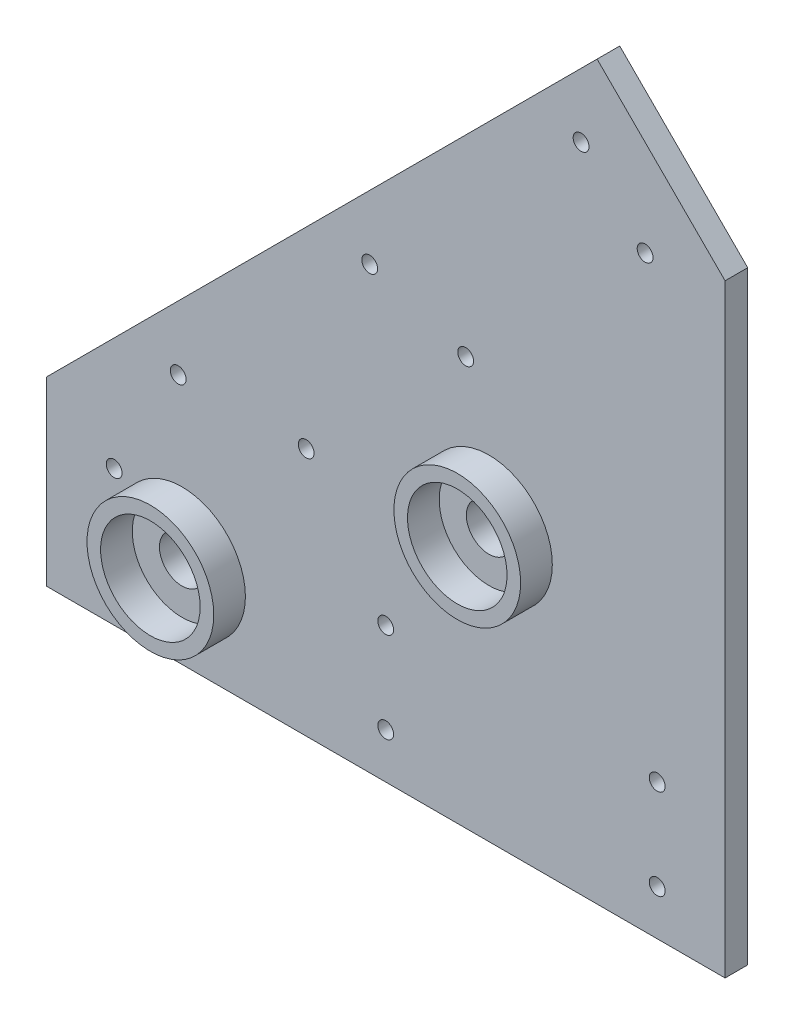
SolidWorks part; units mm, degrees
ref_plane "Front Plane" through (0, 0, 0) normal (0, 0, 1) x (1, 0, 0)
ref_plane "Top Plane" through (0, 0, 0) normal (0, 1, 0) x (1, 0, 0)
ref_plane "Right Plane" through (0, 0, 0) normal (1, 0, 0) x (0, 0, -1)
sketch "Sketch1" plane through (0, 0, 0) normal (0, 0, 1) x (1, 0, 0)
  line L0 (-75, 20) -> (46.7157, 141.7157)
  line L1 (-18.4315, 20) -> (75, 20) construction
  line L2 (-75, 20) -> (-75, -20)
  line L3 (-75, -20) -> (75, -20)
  line L4 (75, 20) -> (75, -20)
  line L5 (-75, 20) -> (75, -20) construction
  line L6 (-75, -20) -> (75, 20) construction
  line L7 (-75, -20) -> (75, -20)
  line L11 (46.7157, 141.7157) -> (75, 113.4315)
  line L12 (75, 113.4315) -> (-18.4315, 20) construction
  line L13 (-75, 0) -> (75, 0) construction
  line L14 (-75, 10) -> (75, 10) construction
  line L15 (-75, -10) -> (75, -10) construction
  line L16 (60.8579, 127.5736) -> (-46.7157, 20) construction
  line L17 (-75, 20) -> (-18.4315, 20) construction
  line L18 (53.7868, 134.6447) -> (-60.8579, 20) construction
  line L19 (67.9289, 120.5025) -> (-32.5736, 20) construction
  line L20 (75, 113.4315) -> (75, 20)
  line L21 (43.1802, 124.0381) -> (57.3223, 109.8959) construction
  line L22 (60, -10) -> (60, 10) construction
  line L23 (-60, -10) -> (-60, 10) construction
  circle A0 centre (-45, 0) radius 5
  circle A1 centre (22.8199, 40) radius 5
  circle A2 centre (-60, -10) radius 1.75
  circle A3 centre (0, 10) radius 1.75
  circle A4 centre (60, -10) radius 1.75
  circle A5 centre (-45.8579, 35) radius 1.75
  circle A6 centre (43.1802, 124.0381) radius 1.75
  circle A8 centre (-17.5736, 35) radius 1.75
  circle A9 centre (57.3223, 109.8959) radius 1.75
  circle A10 centre (22.8199, 40) radius 4 construction
  circle A11 centre (-3.5355, 77.3223) radius 1.75
  circle A12 centre (17.6777, 70.2513) radius 1.75
  circle A13 centre (60, 10) radius 1.75
  circle A14 centre (-60, 10) radius 1.75
  circle A15 centre (0, -10) radius 1.75
  point P0 (0, 0)
  dimension "D8" = 10
  dimension "D11" = 10
  dimension "D12" = 3.5
  dimension "D1" = 40
  dimension "D2" = 40
  dimension "D3" = 45
  dimension "D4" = 10
  dimension "D5" = 10
  dimension "D6" = 10
  dimension "D7" = 10
  dimension "D9" = 30
  dimension "D10" = 150
  dimension "D13" = 15
  dimension "D14" = 15
  dimension "D15" = 15
  dimension "D16" = 15
extrude "Boss-Extrude1" add sketch "Sketch1" along normal blind 5 contours L20 L11 L0 L2 L3 L4 A0 region at (14.2199, 41.208, 0)
sketch "Sketch2" plane through (0, 0, 5) normal (0, 0, 1) x (1, 0, 0)
  circle A0 centre (-45, 0) radius 11
  circle A1 centre (-45, 0) radius 14
  circle A2 centre (22.8199, 40) radius 11
  circle A3 centre (22.8199, 40) radius 14
  dimension "D1" = 22
  dimension "D2" = 28
  dimension "D3" = 22
  dimension "D4" = 28
extrude "Boss-Extrude2" add sketch "Sketch2" along normal blind 7
